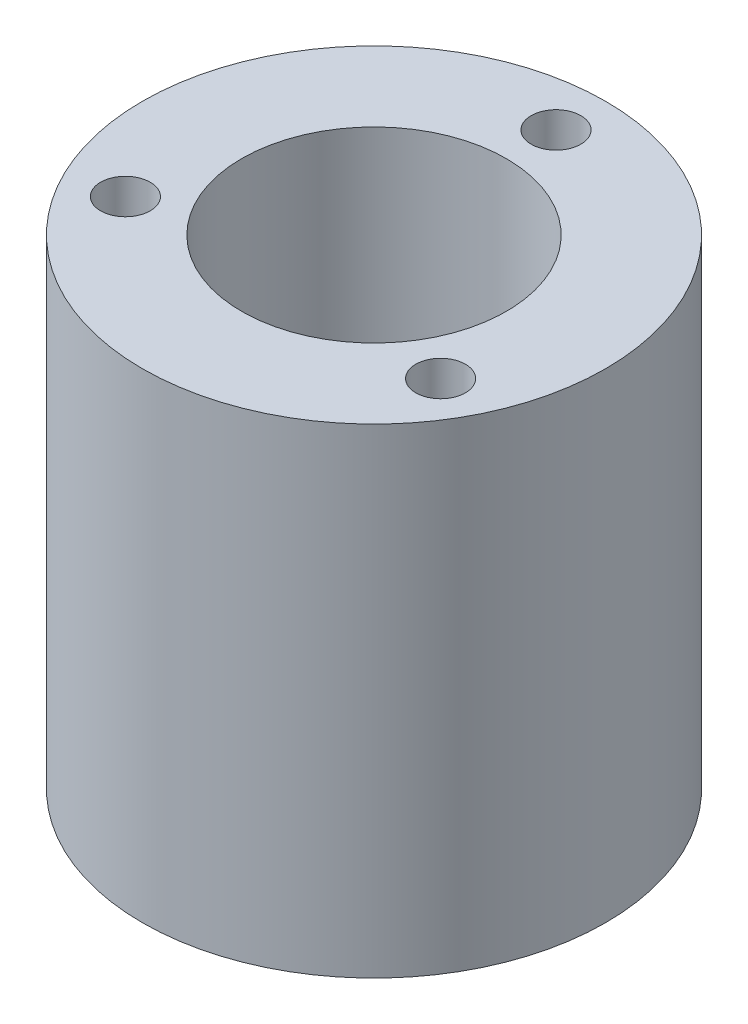
SolidWorks part; units mm, degrees
ref_plane "Plan de face" through (0, 0, 0) normal (0, 0, 1) x (1, 0, 0)
ref_plane "Plan de dessus" through (0, 0, 0) normal (0, 1, 0) x (1, 0, 0)
ref_plane "Plan de droite" through (0, 0, 0) normal (1, 0, 0) x (0, 0, -1)
sketch "Esquisse1" plane through (0, 0, 0) normal (0, 0, 1) x (1, 0, 0)
  line L0 (0, 0) -> (0, 32) construction
  line L1 (8, 0) -> (8, 1.5)
  line L2 (8, 1.5) -> (14, 1.5)
  line L3 (14, 1.5) -> (14, 30.5)
  line L4 (8, 0) -> (3, 0)
  line L7 (3, 0) -> (3, 32)
  line L8 (14, 16) -> (3, 16) construction
  line L9 (3, 16) -> (0, 16) construction
  line L12 (8, 32) -> (3, 32)
  line L13 (8, 30.5) -> (14, 30.5)
  line L14 (8, 32) -> (8, 30.5)
  dimension "D2" = 6
  dimension "D4" = 1.5
  dimension "D5" = 16
  dimension "D6" = 28
  dimension "D7" = 32
revolve "Révolution1" add sketch "Esquisse1" angle 360 about L0
sketch "Esquisse2" plane through (0, 30.5, 0) normal (0, 1, 0) x (1, 0, 0)
  circle A0 centre (0, 0) radius 11 construction
  circle A1 centre (0, 11) radius 1.5
  circle A2 centre (9.5263, -5.5) radius 1.5
  circle A3 centre (-9.5263, -5.5) radius 1.5
  point P12 (0, 0)
  dimension "D1" = 22
  dimension "D2" = 3
  dimension "D3" = 3
extrude "Enlèv. mat.-Extru.1" cut sketch "Esquisse2" against normal blind 10
sketch "Esquisse3" plane through (0, 32, 0) normal (0, 1, 0) x (1, 0, 0)
  circle A0 centre (0, 0) radius 8
extrude "Enlèv. mat.-Extru.2" cut sketch "Esquisse3" against normal blind 25
